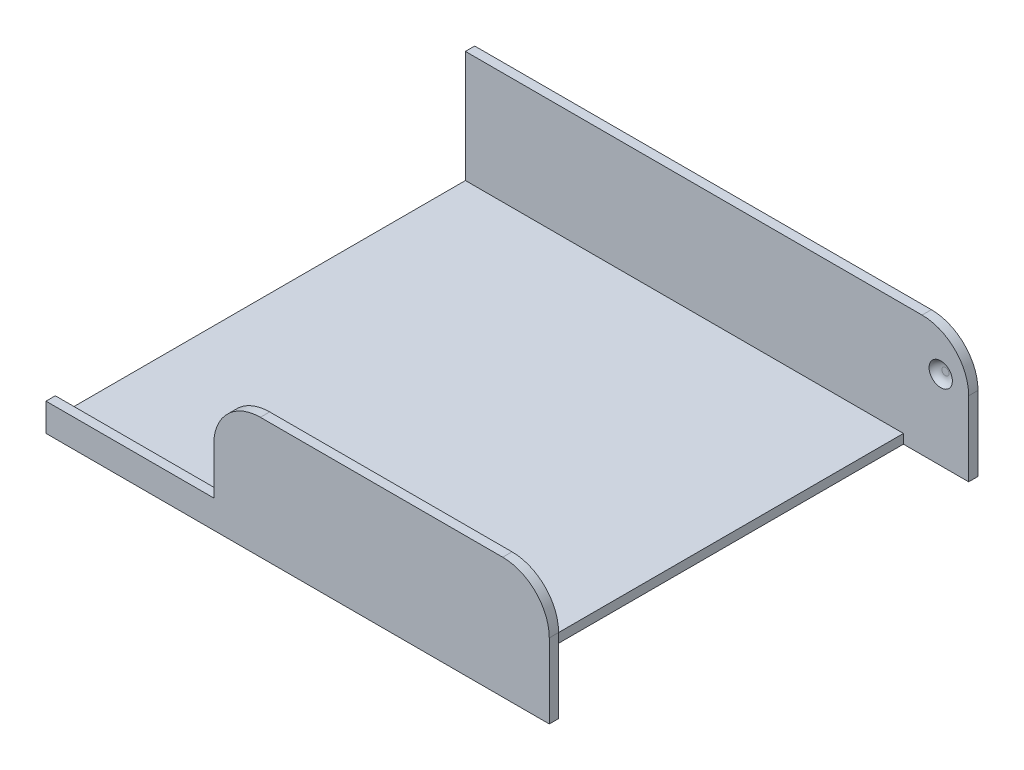
SolidWorks part; units mm, degrees
material "Plain Carbon Steel"
ref_plane "Front Plane" through (0, 0, 0) normal (0, 0, 1) x (1, 0, 0)
ref_plane "Top Plane" through (0, 0, 0) normal (0, 1, 0) x (1, 0, 0)
ref_plane "Right Plane" through (0, 0, 0) normal (1, 0, 0) x (0, 0, -1)
sketch "Sketch1" plane through (0, 0, 0) normal (0, 1, 0) x (1, 0, 0)
  line L1 (0, 88) -> (108, 88)
  line L2 (0, 88) -> (0, 0)
  line L3 (0, 0) -> (108, 0)
  line L4 (108, 88) -> (108, 0)
  line L5 (-2, 90) -> (110, 90)
  line L6 (-2, 90) -> (-2, -2)
  line L7 (-2, -2) -> (110, -2)
  line L8 (110, 90) -> (110, -2)
  dimension "D1" = 108
  dimension "D2" = 88
  dimension "D3" = 0
  dimension "D4" = 0
  dimension "D5" = 92
  dimension "D6" = 2
  dimension "D7" = 112
  dimension "D8" = 2
extrude "Boss-Extrude2" add sketch "Sketch1" along normal blind 2 contours L2 L3 L4 L1
extrude "Boss-Extrude3" add sketch "Sketch1<3>" along normal blind 26
sketch "Sketch1<3>" plane through (0, 0, 0) normal (0, 1, 0) x (1, 0, 0) same geometry as "Sketch1"
sketch "Sketch5" plane through (110, 0, 0) normal (1, 0, 0) x (0, 0, -1)
  line L0 (-2, 26) -> (-2, 0) construction
  line L1 (-2, 26) -> (90, 26)
  line L2 (-2, 26) -> (-2, 0)
  line L3 (-2, 0) -> (90, 0)
  line L4 (90, 26) -> (90, 0)
  line L5 (90, 26) -> (90, 0) construction
  line L6 (-2, 26) -> (90, 26) construction
  line L7 (-2, 0) -> (90, 0) construction
  dimension "D1" = 0
  dimension "D2" = 0
extrude "Cut-Extrude1" cut sketch "Sketch5" against normal blind 2
sketch "Sketch6" plane through (0, 0, 0) normal (0, 0, -1) x (-1, 0, 0)
  line L0 (-108, 26) -> (-108, 2) construction
  line L2 (2, 26) -> (-108, 26) construction
  circle A0 centre (-102, 17) radius 2.75
  dimension "D2" = 5.5
  dimension "D3" = 9
  dimension "D1" = 6
extrude "Cut-Extrude2" cut sketch "Sketch6" against normal blind 1
sketch "Sketch7" plane through (0, 0, -88) normal (0, 0, 1) x (1, 0, 0)
  line L0 (108, 26) -> (108, 2) construction
  line L2 (108, 26) -> (0, 26) construction
  circle A0 centre (102, 17) radius 2.5
  dimension "D2" = 5
  dimension "D3" = 9
  dimension "D1" = 6
extrude "Cut-Extrude3" cut sketch "Sketch7" against normal blind 1 contours A0
fillet "Fillet1" radius 2 1 edges at (99.25, 17, 1)
fillet "Fillet2" radius 2 1 edges at (104.5, 17, -89)
sketch "Sketch8" plane through (0, 0, -90) normal (0, 0, -1) x (-1, 0, 0)
  line L0 (-108, 26) -> (2, 26) construction
  line L1 (-36, 26) -> (2, 26)
  line L2 (-36, 26) -> (-36, 6)
  line L3 (-36, 6) -> (2, 6)
  line L4 (2, 26) -> (2, 6)
  line L5 (2, 26) -> (2, 0) construction
  line L7 (-108, 0) -> (2, 0) construction
  dimension "D1" = 38
  dimension "D2" = 6
sketch "Sketch9" plane through (0, 0, 2) normal (0, 0, 1) x (1, 0, 0)
  line L0 (-2, 0) -> (108, 0) construction
  line L1 (-2, 26) -> (36, 26)
  line L2 (-2, 26) -> (-2, 6)
  line L3 (-2, 6) -> (36, 6)
  line L4 (36, 26) -> (36, 6)
  dimension "D1" = 6
  dimension "D2" = 38
extrude "Cut-Extrude4" cut sketch "Sketch9" against normal blind 2
sketch "Sketch10" plane through (-2, 0, 0) normal (-1, 0, 0) x (0, 0, 1)
  line L1 (-90, 26) -> (2, 26)
  line L2 (-90, 26) -> (-90, 0)
  line L3 (-90, 0) -> (2, 0)
  line L4 (2, 26) -> (2, 0)
extrude "Cut-Extrude5" cut sketch "Sketch10" against normal blind 2
fillet "Fillet3" radius 10 1 edges at (36, 26, 1)
fillet "Fillet4" radius 10 1 edges at (108, 26, 1)
fillet "Fillet5" radius 10 1 edges at (108, 26, -89)
sketch "Sketch11" plane through (0, 0, 0) normal (0, -1, 0) x (-1, 0, 0)
  line L0 (-108, -2) -> (-108, 90) construction
  line L1 (-108, 0) -> (-94, 0)
  line L2 (-108, 0) -> (-108, 88)
  line L3 (-108, 88) -> (-94, 88)
  line L4 (-94, 0) -> (-94, 88)
  line L5 (0, -2) -> (-108, -2) construction
  line L6 (-108, 90) -> (0, 90) construction
  dimension "D1" = 2
  dimension "D2" = 2
  dimension "D3" = 14
extrude "Cut-Extrude6" cut sketch "Sketch11" against normal blind 2
